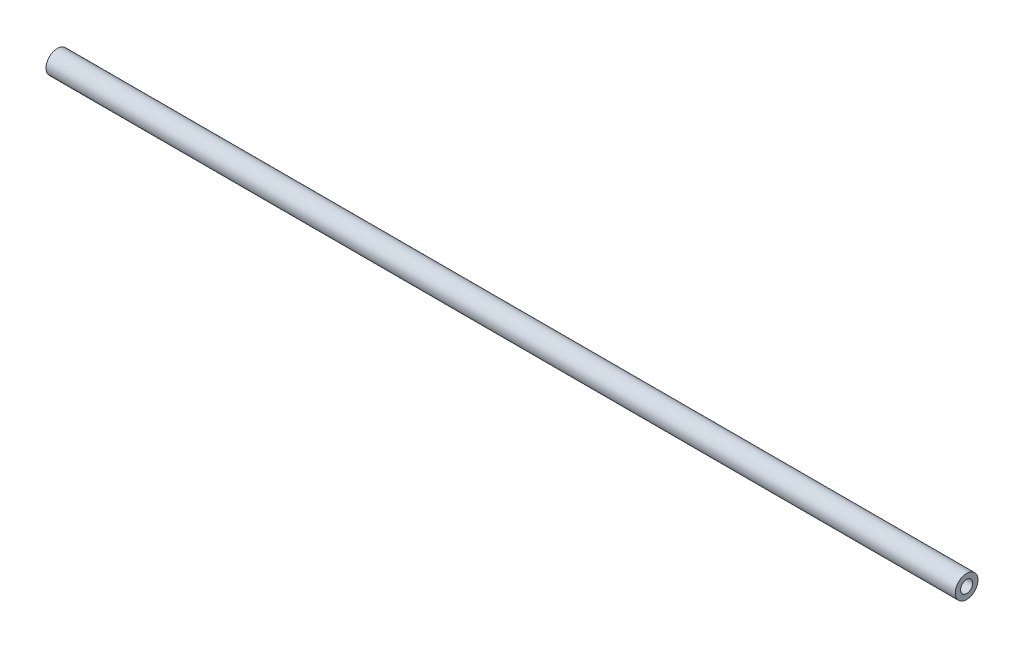
SolidWorks part; units mm, degrees
material "6061-T6 (SS)"
ref_plane "Front" through (0, 0, 0) normal (0, 0, 1) x (1, 0, 0)
ref_plane "Top" through (0, 0, 0) normal (0, 1, 0) x (1, 0, 0)
ref_plane "Right" through (0, 0, 0) normal (1, 0, 0) x (0, 0, -1)
sketch "Sketch1" plane through (0, 0, 0) normal (1, 0, 0) x (0, 0, -1)
  circle A0 centre (0, 0) radius 4.7625
  dimension "D1" = 9.525
extrude "Boss-Extrude1" add sketch "Sketch1" along normal blind 381
hole_wizard "1/4-20 Tapped Hole1" positions "Sketch2" profile "Sketch3" tap size "1/4-20" standard "ANSI Inch"
sketch "Sketch2" plane through (0, 0, 0) normal (-1, 0, 0) x (0, 0, 1)
  point P0 (0, 0)
sketch "Sketch3" plane through (0, 0, 0) normal (0, 1, 0) x (0, 0, 1)
  line L0 (0, 0) -> (0, 18.0438)
  line L1 (0, 18.0438) -> (2.5527, 16.51)
  line L2 (2.5527, 16.51) -> (2.5527, 0)
  line L5 (2.5527, 0) -> (0, 0)
  line L10 (0, 18.0438) -> (-2.5527, 16.51) construction
  line L11 (0, -6.35) -> (0, 107.95) construction
  dimension "Tap Drill Dia." = 5.1054
  dimension "Tap Drill Depth" = 16.51
  dimension "Drill Angle" = 118
cosmetic thread "Hole Thread1"
hole_wizard "1/4-20 Tapped Hole2" positions "Sketch4" profile "Sketch5" tap size "1/4-20" standard "ANSI Inch"
sketch "Sketch4" plane through (381, 0, 0) normal (1, 0, 0) x (0, 0, -1)
  point P0 (0, 0)
sketch "Sketch5" plane through (381, 0, 0) normal (0, 1, 0) x (0, 0, -1)
  line L0 (0, 0) -> (0, 18.0438)
  line L1 (0, 18.0438) -> (2.5527, 16.51)
  line L2 (2.5527, 16.51) -> (2.5527, 0)
  line L5 (2.5527, 0) -> (0, 0)
  line L10 (0, 18.0438) -> (-2.5527, 16.51) construction
  line L11 (0, -6.35) -> (0, 107.95) construction
  dimension "Tap Drill Dia." = 5.1054
  dimension "Tap Drill Depth" = 16.51
  dimension "Drill Angle" = 118
cosmetic thread "Hole Thread2" parameters "D1"=12.7, "D2"=6.35
